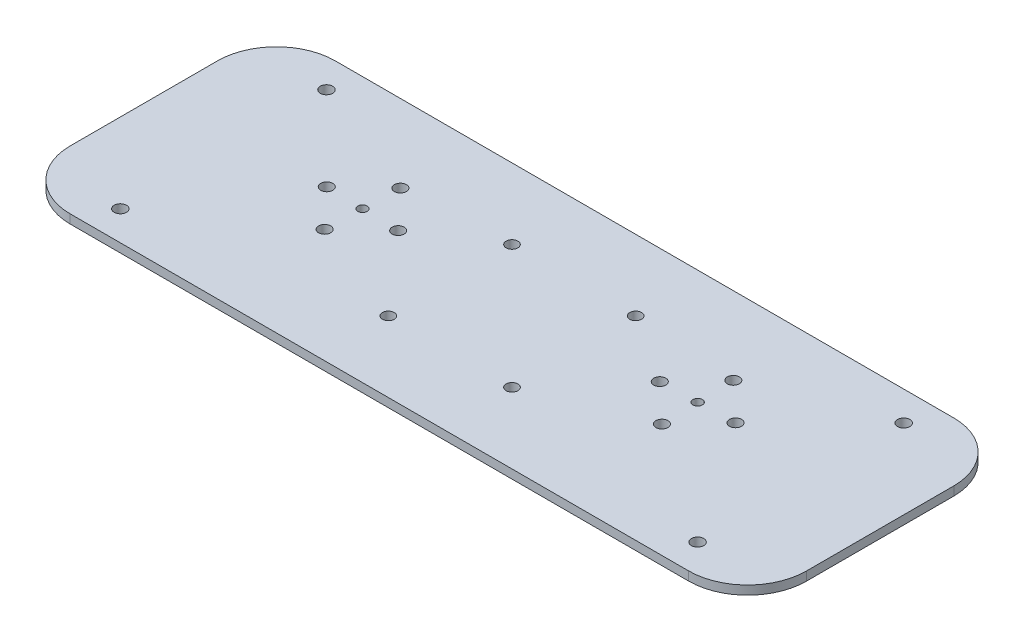
SolidWorks part; units mm, degrees
ref_plane "前视基准面" through (0, 0, 0) normal (0, 0, 1) x (1, 0, 0)
ref_plane "上视基准面" through (0, 0, 0) normal (0, 1, 0) x (1, 0, 0)
ref_plane "右视基准面" through (0, 0, 0) normal (1, 0, 0) x (0, 0, -1)
sketch "草图1" plane through (0, 0, 0) normal (0, 0, 1) x (1, 0, 0)
  line L1 (-125, -1.5) -> (125, -1.5)
  line L2 (-125, -1.5) -> (-125, 1.5)
  line L3 (-125, 1.5) -> (125, 1.5)
  line L4 (125, -1.5) -> (125, 1.5)
  line L5 (-125, -1.5) -> (125, 1.5) construction
  line L6 (-125, 1.5) -> (125, -1.5) construction
  point P0 (0, 0)
  dimension "D1" = 3
  dimension "D2" = 250
extrude "凸台-拉伸1" add sketch "草图1" along normal mid plane 90
sketch "草图2" plane through (0, 1.5, 0) normal (0, 1, 0) x (1, 0, 0)
  line L0 (-21, 21) -> (21, 21) construction
  line L1 (21, 21) -> (21, -21) construction
  line L2 (21, -21) -> (-21, -21) construction
  line L3 (-21, -21) -> (-21, 21) construction
  circle A0 centre (-21, 21) radius 2
  circle A1 centre (21, 21) radius 2
  circle A2 centre (21, -21) radius 2
  circle A3 centre (-21, -21) radius 2
  point P8 (21, 0)
  point P9 (0, 21)
  dimension "D1" = 4
  dimension "D2" = 42
  dimension "D3" = 42
extrude "切除-拉伸1" cut sketch "草图2" against normal through all
fillet "圆角1" radius 20 4 edges at (125, 0, 45) (-125, 0, 45) (-125, 0, -45) (125, 0, -45)
sketch "草图4" plane through (0, -1.5, 0) normal (0, -1, 0) x (1, 0, 0)
  line L0 (-98, -35) -> (-98, 35) construction
  line L1 (-98, 35) -> (98, 35) construction
  line L2 (98, 35) -> (98, -35) construction
  line L3 (98, -35) -> (-98, -35) construction
  circle A0 centre (-98, -35) radius 2.1
  circle A1 centre (-98, 35) radius 2.1
  circle A2 centre (98, 35) radius 2.1
  circle A3 centre (98, -35) radius 2.1
  point P8 (0, -35)
  point P9 (-98, 0)
  dimension "D1" = 4.2
  dimension "D2" = 70
  dimension "D3" = 196
extrude "切除-拉伸3" cut sketch "草图4" against normal blind 10
sketch "草图5" plane through (0, -1.5, 0) normal (0, -1, 0) x (1, 0, 0)
  circle A0 centre (57.2731, 6.3593) radius 2.05 construction
  circle A1 centre (69.3984, -6.5045) radius 2.05 construction
  circle A2 centre (44.4093, -5.7659) radius 2.05 construction
  circle A3 centre (56.5346, -18.6297) radius 2.05 construction
  circle A4 centre (57.2731, 6.3593) radius 2.05
  circle A5 centre (69.3984, -6.5045) radius 2.05
  circle A6 centre (44.4093, -5.7659) radius 2.05
  circle A7 centre (56.5346, -18.6297) radius 2.05
extrude "切除-拉伸4" cut sketch "草图5" against normal blind 4
sketch "草图6" plane through (0, 1.5, 0) normal (0, 1, 0) x (1, 0, 0)
  circle A0 centre (56.9038, 6.1352) radius 17 construction
  circle A1 centre (56.9038, 6.1352) radius 17 construction
  circle A2 centre (56.9038, 6.1352) radius 1.6
  dimension "D1" = 3.2
extrude "切除-拉伸5" cut sketch "草图6" against normal blind 4
mirror "镜向1" about plane through (0, 0, 0) normal (1, 0, 0) of "切除-拉伸5", "切除-拉伸4"
